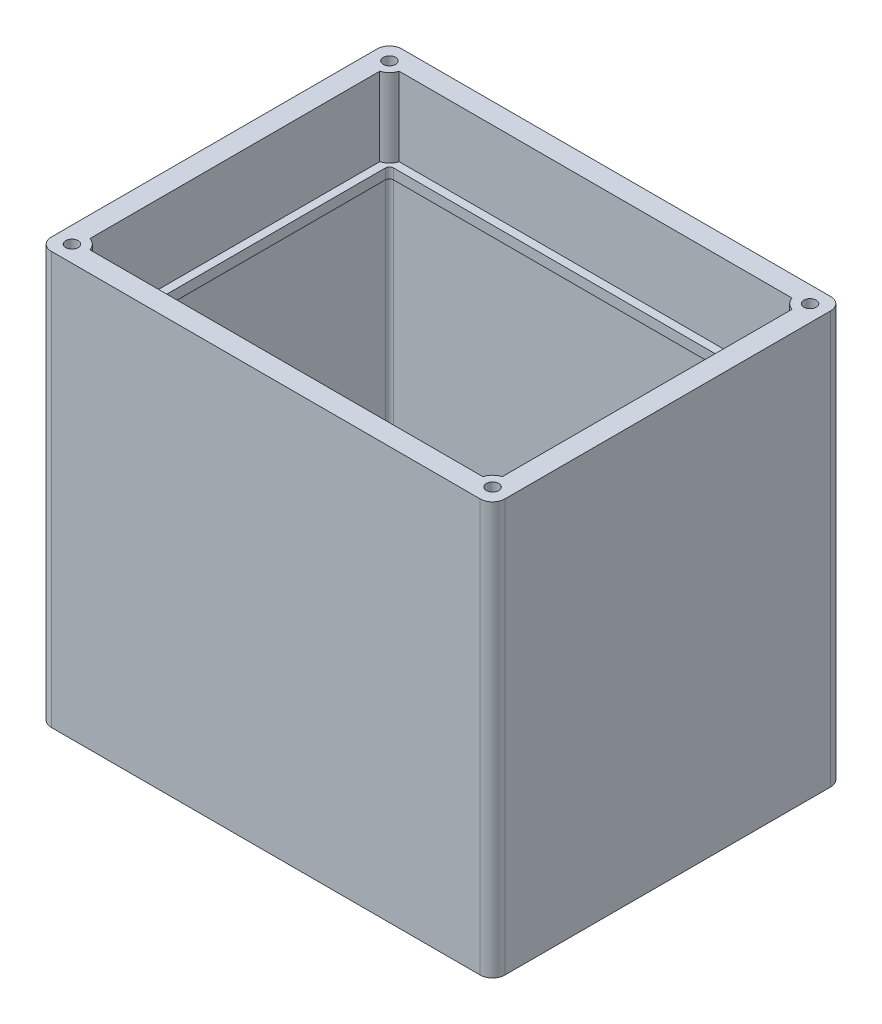
SolidWorks part; units mm, degrees
ref_plane "Front Plane" through (0, 0, 0) normal (0, 0, 1) x (1, 0, 0)
ref_plane "Top Plane" through (0, 0, 0) normal (0, 1, 0) x (1, 0, 0)
ref_plane "Right Plane" through (0, 0, 0) normal (1, 0, 0) x (0, 0, -1)
sketch "Sketch1" plane through (0, 0, 0) normal (0, 1, 0) x (1, 0, 0)
  line L1 (0, 0) -> (100, 0)
  line L2 (0, 0) -> (0, 75)
  line L3 (0, 75) -> (100, 75)
  line L4 (100, 0) -> (100, 75)
  dimension "D1" = 100
  dimension "D2" = 75
extrude "Boss-Extrude1" add sketch "Sketch1" along normal blind 95
shell "Shell1" thickness 5 removed face at (50, 95, -37.5) outward yes
fillet "Fillet2" radius 3 4 edges at (105, 45, -80) (105, 45, 5) (-5, 45, 5) (-5, 45, -80)
sketch "Sketch6" plane through (0, 95, 0) normal (0, 1, 0) x (1, 0, 0)
  line L13 (50, 80) -> (50, -5) construction
  line L14 (102, 80) -> (-2, 80) construction
  line L15 (-2, -5) -> (102, -5) construction
  line L16 (-5, 37.5) -> (105, 37.5) construction
  line L17 (101, -1) -> (101, 76)
  line L18 (-1, -1) -> (101, -1)
  line L19 (-1, 76) -> (-1, -1)
  line L20 (101, 76) -> (-1, 76)
  line L21 (101, -1) -> (101, 76)
  line L22 (-1, -1) -> (101, -1)
  line L23 (-1, 76) -> (-1, -1)
  line L24 (101, 76) -> (-1, 76)
  line L25 (-5, 77) -> (-5, -2) construction
  line L26 (105, -2) -> (105, 77) construction
  circle A0 centre (-1, 76) radius 1.5
  circle A1 centre (-1, 76) radius 3.5
  circle A2 centre (101, 76) radius 1.5
  circle A3 centre (101, 76) radius 3.5
  circle A4 centre (101, -1) radius 1.5
  circle A5 centre (101, -1) radius 3.5
  circle A6 centre (-1, -1) radius 1.5
  circle A7 centre (-1, -1) radius 3.5
  dimension "D2" = 7
  dimension "D3" = 3
  dimension "D1" = 1
extrude "Boss-Extrude4" add sketch "Sketch6" against normal blind 19 contours A7 | A1 | A3 | A5
extrude "Cut-Extrude2" cut sketch "Sketch6<4>" against normal blind 15 contours A6 | A4 | A0 | A2
sketch "Sketch6<4>" plane through (0, 95, 0) normal (0, 1, 0) x (1, 0, 0) same geometry as "Sketch6"
fillet "Fillet3" radius 1 4 edges at (100, 38, -75) (100, 38, 0) (0, 38, -75) (0, 38, 0)
ref_plane "Plane2" through (0, 75, 0) normal (0, 1, 0) x (1, 0, 0)
sketch "Sketch8" plane through (0, 75, 0) normal (0, 1, 0) x (1, 0, 0)
  line L0 (50, 75) -> (50, 0) construction
  line L1 (97.6459, 75) -> (2.3541, 75) construction
  line L2 (2.3541, 0) -> (97.6459, 0) construction
  line L3 (0, 37.5) -> (100, 37.5) construction
  line L4 (0, 74) -> (0, 1) construction
  line L5 (100, 1) -> (100, 74) construction
  line L6 (2, 73) -> (98, 73)
  line L7 (0, 0) -> (100, 0)
  line L8 (0, 0) -> (0, 75)
  line L9 (0, 75) -> (100, 75)
  line L10 (100, 0) -> (100, 75)
  line L11 (0, 0) -> (100, 75) construction
  line L12 (0, 75) -> (100, 0) construction
  line L13 (98, 2) -> (98, 73)
  line L14 (2, 2) -> (98, 2)
  line L15 (2, 2) -> (2, 73)
  point P12 (50, 37.5)
  dimension "D1" = 2
extrude "Boss-Extrude5" add sketch "Sketch8" along normal blind 1 and the other way blind 1.5
fillet "Fillet4" radius 1 4 edges at (98, 74.75, -73) (98, 74.75, -2) (2, 74.75, -2) (2, 74.75, -73)
